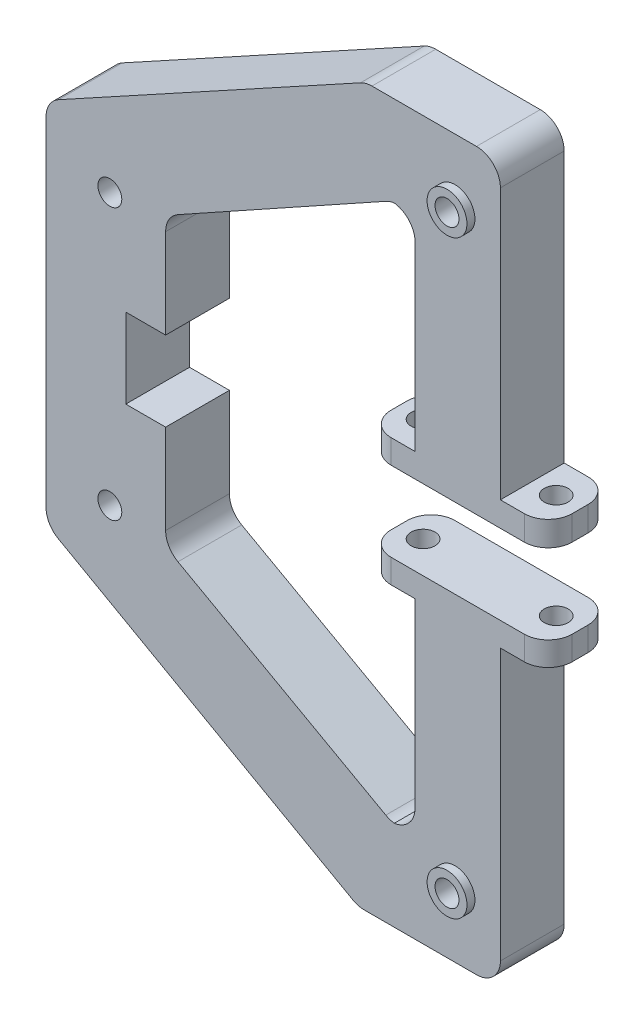
SolidWorks part; units mm, degrees
ref_plane "前视基准面" through (0, 0, 0) normal (0, 0, 1) x (1, 0, 0)
ref_plane "上视基准面" through (0, 0, 0) normal (0, 1, 0) x (1, 0, 0)
ref_plane "右视基准面" through (0, 0, 0) normal (1, 0, 0) x (0, 0, -1)
sketch "草图1" plane through (0, 0, 0) normal (0, 0, 1) x (1, 0, 0)
  line L6 (-70, 23) -> (-70, 5)
  line L11 (-29.8827, 45) -> (-13.8412, 45)
  line L14 (-70, 23) -> (-29.8827, 45)
  line L15 (-70, -23) -> (-30.8397, -45)
  line L16 (-55, 18) -> (-26.7, 33.7222)
  line L17 (-55, -18) -> (-26.7, -33.7222)
  line L18 (-55, 18) -> (-55, 10)
  line L20 (-55, 10) -> (-55, 18)
  line L21 (-55, -18) -> (-55, -10)
  line L22 (-55, -10) -> (-55, -18)
  line L25 (-23.7, 33.7222) -> (-23.7, 8)
  line L28 (-23.7, 5) -> (-29.7, 5)
  line L29 (-55, 5) -> (-55, 10)
  line L32 (-70, 5) -> (-70, -5)
  line L33 (-55, -5) -> (-55, -10)
  line L35 (-60, -5) -> (-60, 5)
  line L37 (-70, -5) -> (-70, -23)
  line L38 (-60, 5) -> (-55, 5)
  line L39 (-60, -5) -> (-55, -5)
  line L40 (-23.7, 33.7222) -> (-26.7, 33.7222)
  line L41 (-13.8744, 5) -> (-7, 5)
  line L42 (-13, 45) -> (-13.8412, 45)
  line L44 (-13.8744, -5) -> (-23.7, -5)
  line L45 (-23.7, -33.7222) -> (-26.7, -33.7222)
  line L46 (-30.8397, -45) -> (-13, -45)
  line L47 (-13, 45) -> (-13, 8.1002)
  line L48 (-29.7, 5) -> (-29.7, 8)
  line L49 (-23.7, 8) -> (-29.7, 8)
  line L50 (-7, 5) -> (-7, 8.1002)
  line L51 (-7, 8.1002) -> (-13, 8.1002)
  line L52 (-13.8744, 5) -> (-23.7, 5)
  line L53 (-23.7, -8) -> (-23.7, -33.7222)
  line L54 (-23.7, -5) -> (-29.7, -5)
  line L55 (-29.7, -5) -> (-29.7, -8)
  line L56 (-29.7, -8) -> (-23.7, -8)
  line L57 (-13.8744, -5) -> (-7, -5)
  line L58 (-7, -5) -> (-7, -8)
  line L59 (-7, -8) -> (-13, -8)
  line L60 (-13, -8) -> (-13, -45)
  point P0 (0, 0)
  point P4 (-70, 0)
extrude "凸台-拉伸1" add sketch "草图1" along normal blind 8 contours L11 L14 L15 L21 L17 L18 L16 region at (-49.4131, 33.0367, 0)
sketch "草图2" plane through (0, 0, 8) normal (0, 0, 1) x (1, 0, 0)
  circle A0 centre (-62, 17) radius 1.5
  circle A1 centre (-62, -17) radius 1.5
  circle A2 centre (-18.6987, 37) radius 1.5
  circle A3 centre (-18.6987, -37) radius 1.5
extrude "切除-拉伸1" cut sketch "草图2" against normal through all
sketch "草图7" plane through (0, 0, 8) normal (0, 0, 1) x (1, 0, 0)
  circle A4 centre (-18.6987, 37) radius 1.5
  circle A5 centre (-18.6987, 37) radius 2.5
  circle A6 centre (-18.6987, -37) radius 1.5
  circle A7 centre (-18.6987, -37) radius 2.5
extrude "凸台-拉伸5" add sketch "草图7" along normal blind 1
sketch "草图8" plane through (0, 8, 0) normal (0, 1, 0) x (1, 0, 0)
  circle A0 centre (-26.7, -4) radius 1.5
  circle A1 centre (-10, -4) radius 1.5
extrude "切除-拉伸2" cut sketch "草图8" against normal blind 20 and the other way blind 10
fillet "圆角1" radius 3 12 edges at (-13, 45, 4) (-29.8827, 45, 4) (-13, -45, 4) (-30.8397, -45, 4) (-70, -23, 4) (-70, 23, 4) (-55, -18, 4) (-55, 18, 4) (-26.7, -33.7222, 4) (-23.7, -33.7222, 4) (-26.7, 33.7222, 4) (-23.7, 33.7222, 4)
fillet "圆角2" radius 3 8 edges at (-29.7, 6.5, 0) (-29.7, -6.5, 0) (-29.7, 6.5, 8) (-29.7, -6.5, 8) (-7, -6.5, 0) (-7, -6.5, 8) (-7, 6.5501, 0) (-7, 6.5501, 8)
